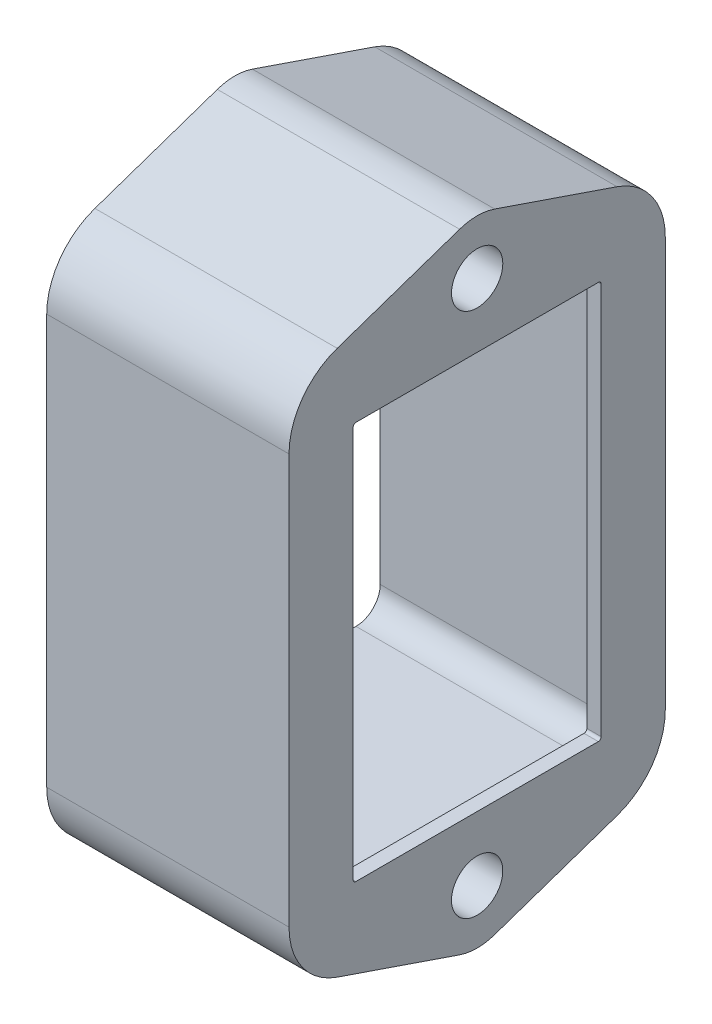
SolidWorks part; units mm, degrees
ref_plane "Alzado" through (0, 0, 0) normal (0, 0, 1) x (1, 0, 0)
ref_plane "Planta" through (0, 0, 0) normal (0, 1, 0) x (1, 0, 0)
ref_plane "Vista lateral" through (0, 0, 0) normal (1, 0, 0) x (0, 0, -1)
sketch "Croquis2" plane through (0, 0, 0) normal (1, 0, 0) x (0, 0, -1)
  line L0 (0, -55.062) -> (0, 49.3875) construction
  line L1 (-26.4, -41.4649) -> (-26.4, 16.0397)
  line L2 (-19.6372, 25.5012) -> (-2.4603, 31.3781)
  line L3 (19.6372, 25.5012) -> (2.4603, 31.3781)
  line L4 (26.4, -41.4649) -> (26.4, 16.0397)
  line L5 (19.6372, -50.9265) -> (2.4603, -56.8034)
  line L6 (20, -40.2126) -> (20, 14.7874) construction
  line L7 (17, 17.7874) -> (0, 17.7874) construction
  line L8 (0, 17.7874) -> (-17, 17.7874) construction
  line L9 (-20, 14.7874) -> (-20, -40.2126) construction
  line L10 (-17, -43.2126) -> (0, -43.2126) construction
  line L11 (0, -43.2126) -> (17, -43.2126) construction
  line L12 (20.4, -40.2126) -> (20.4, 14.7874)
  line L13 (17, 18.1874) -> (0, 18.1874)
  line L14 (0, 18.1874) -> (-17, 18.1874)
  line L15 (-20.4, 14.7874) -> (-20.4, -40.2126)
  line L16 (-17, -43.6126) -> (0, -43.6126)
  line L17 (0, -43.6126) -> (17, -43.6126)
  line L18 (-19.6372, -50.9265) -> (-2.4603, -56.8034)
  line L19 (-39.7632, -12.7126) -> (39.8458, -12.7126) construction
  circle A0 centre (0, 24.1874) radius 3.6
  arc A1 (2.4603, 31.3781) -> (-2.4603, 31.3781) centre (0, 24.1874) ccw
  arc A2 (-19.6372, 25.5012) -> (-26.4, 16.0397) centre (-16.4, 16.0397) ccw
  arc A3 (19.6372, 25.5012) -> (26.4, 16.0397) centre (16.4, 16.0397) cw
  arc A4 (20, 14.7874) -> (17, 17.7874) centre (17, 14.7874) ccw construction
  arc A5 (-17, 17.7874) -> (-20, 14.7874) centre (-17, 14.7874) ccw construction
  arc A6 (-20, -40.2126) -> (-17, -43.2126) centre (-17, -40.2126) ccw construction
  arc A7 (17, -43.2126) -> (20, -40.2126) centre (17, -40.2126) ccw construction
  arc A8 (20.4, 14.7874) -> (17, 18.1874) centre (17, 14.7874) ccw
  arc A9 (-17, 18.1874) -> (-20.4, 14.7874) centre (-17, 14.7874) ccw
  arc A10 (-20.4, -40.2126) -> (-17, -43.6126) centre (-17, -40.2126) ccw
  arc A11 (17, -43.6126) -> (20.4, -40.2126) centre (17, -40.2126) ccw
  circle A12 centre (0, -49.6126) radius 3.6
  arc A13 (2.4603, -56.8034) -> (-2.4603, -56.8034) centre (0, -49.6126) cw
  arc A14 (19.6372, -50.9265) -> (26.4, -41.4649) centre (16.4, -41.4649) ccw
  arc A15 (-19.6372, -50.9265) -> (-26.4, -41.4649) centre (-16.4, -41.4649) cw
  point P36 (-20.4, -12.7126)
  point P43 (-26.4, 23.1874)
  point P53 (26.4, -12.7126)
  point P58 (-26.4, -12.7126)
  dimension "D5" = 7.2
  dimension "D2" = 4
  dimension "D7" = 10
  dimension "D3" = 6
  dimension "D4" = 6
  dimension "D6" = 5
  dimension "D1" = 0.4
extrude "Saliente-Extruir1" add sketch "Croquis2" against normal blind 32 and the other way blind 2
sketch "Croquis3" plane through (2, 0, 0) normal (1, 0, 0) x (0, 0, -1)
  line L0 (-17, -43.6126) -> (17, -43.6126) construction
  line L1 (20.4, -40.2126) -> (20.4, 14.7874) construction
  line L2 (-20.4, 14.7874) -> (-20.4, -40.2126) construction
  line L3 (17, 18.1874) -> (-17, 18.1874) construction
  line L4 (-17, -43.6126) -> (17, -43.6126)
  line L5 (20.4, -40.2126) -> (20.4, 14.7874)
  line L6 (-20.4, 14.7874) -> (-20.4, -40.2126)
  line L7 (17, 18.1874) -> (-17, 18.1874)
  line L8 (-17, -40.6126) -> (17, -40.6126)
  line L9 (17.4, -40.2126) -> (17.4, 14.7874)
  line L10 (17, 15.1874) -> (-17, 15.1874)
  line L11 (-17.4, 14.7874) -> (-17.4, -40.2126)
  arc A0 (-20.4, -40.2126) -> (-17, -43.6126) centre (-17, -40.2126) ccw construction
  arc A1 (17, -43.6126) -> (20.4, -40.2126) centre (17, -40.2126) ccw construction
  arc A2 (20.4, 14.7874) -> (17, 18.1874) centre (17, 14.7874) ccw construction
  arc A3 (-17, 18.1874) -> (-20.4, 14.7874) centre (-17, 14.7874) ccw construction
  arc A4 (-20.4, -40.2126) -> (-17, -43.6126) centre (-17, -40.2126) ccw
  arc A5 (17, -43.6126) -> (20.4, -40.2126) centre (17, -40.2126) ccw
  arc A6 (20.4, 14.7874) -> (17, 18.1874) centre (17, 14.7874) ccw
  arc A7 (-17, 18.1874) -> (-20.4, 14.7874) centre (-17, 14.7874) ccw
  arc A8 (17, -40.6126) -> (17.4, -40.2126) centre (17, -40.2126) ccw
  arc A9 (17.4, 14.7874) -> (17, 15.1874) centre (17, 14.7874) ccw
  arc A10 (-17, 15.1874) -> (-17.4, 14.7874) centre (-17, 14.7874) ccw
  arc A11 (-17.4, -40.2126) -> (-17, -40.6126) centre (-17, -40.2126) ccw
  dimension "D1" = 3
extrude "Saliente-Extruir2" add sketch "Croquis3" against normal blind 2
sketch "Croquis4" plane through (-32, 0, 0) normal (-1, 0, 0) x (0, 0, 1)
  line L0 (20.4, 14.7874) -> (20.4, -40.2126) construction
  line L1 (26.4, 16.0397) -> (26.4, -41.4649) construction
  line L2 (20.4, 14.7874) -> (20.4, -40.2126) construction
  line L3 (26.4, 16.0397) -> (26.4, -41.4649) construction
